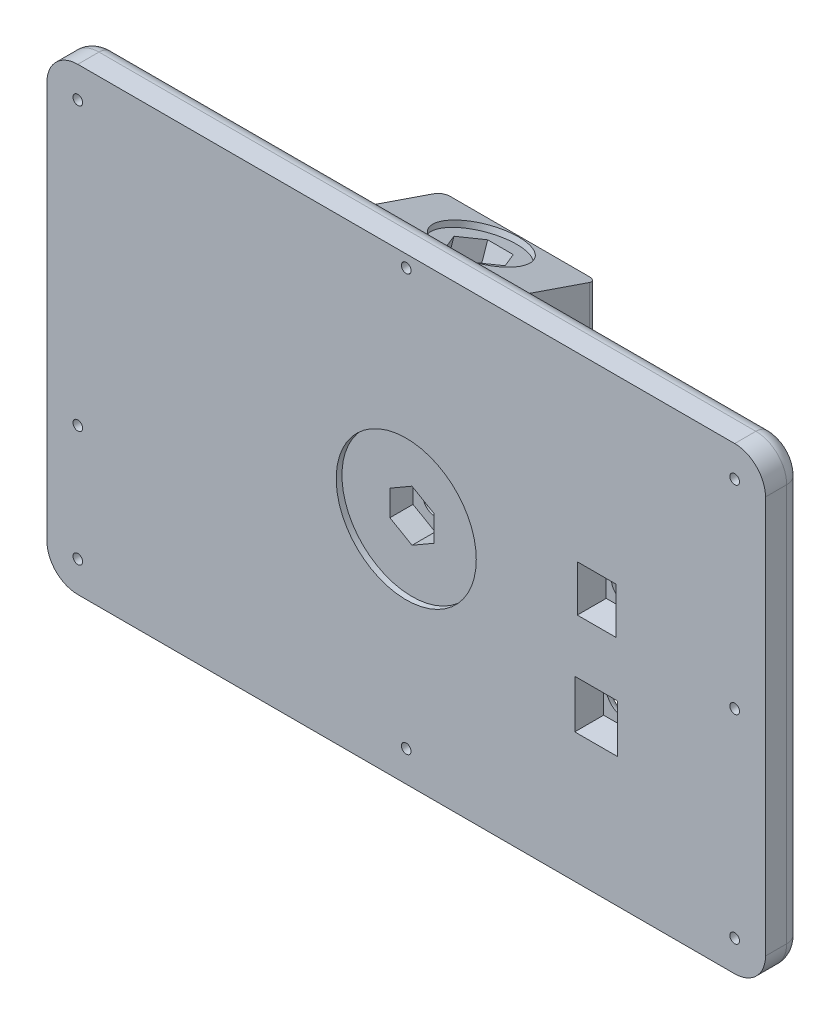
SolidWorks part; units mm, degrees
ref_plane "Front Plane" through (0, 0, 0) normal (0, 0, 1) x (1, 0, 0)
ref_plane "Top Plane" through (0, 0, 0) normal (0, 1, 0) x (1, 0, 0)
ref_plane "Right Plane" through (0, 0, 0) normal (1, 0, 0) x (0, 0, -1)
sketch "Sketch1" plane through (0, 0, 0) normal (0, 0, 1) x (1, 0, 0)
  line L0 (-89.2392, 47.2125) -> (-89.2392, -53.9075)
  line L1 (-83.1292, 39.4025) -> (73.3008, 39.4025)
  line L2 (-83.1292, 39.4025) -> (-83.1292, -49.7475)
  line L3 (-83.1292, -49.7475) -> (73.3008, -49.7475)
  line L4 (73.3008, 39.4025) -> (73.3008, -49.7475)
  line L5 (-88.7392, 46.7125) -> (76.1808, 46.7125)
  line L6 (-88.7392, 46.7125) -> (-88.7392, -53.4075)
  line L7 (-88.7392, -53.4075) -> (76.1808, -53.4075)
  line L8 (76.1808, 46.7125) -> (76.1808, -53.4075)
  line L9 (-89.2392, -53.9075) -> (76.6808, -53.9075)
  line L10 (76.6808, 47.2125) -> (76.6808, -53.9075)
  line L11 (-89.2392, 47.2125) -> (76.6808, 47.2125)
  line L12 (-98.1292, 46.4025) -> (-98.1292, -56.7475)
  line L13 (-90.1292, -64.7475) -> (80.3008, -64.7475)
  line L14 (88.3008, 46.4025) -> (88.3008, -56.7475)
  line L15 (-90.1292, 54.4025) -> (80.3008, 54.4025)
  line L16 (-98.1292, 54.4025) -> (-98.1292, -64.7475) construction
  line L17 (-98.1292, 54.4025) -> (88.3008, 54.4025) construction
  line L18 (-98.1292, -64.7475) -> (88.3008, -64.7475) construction
  line L19 (88.3008, 54.4025) -> (88.3008, -64.7475) construction
  line L21 (-21.7192, 47.2125) -> (-38.9092, 47.2125)
  line L22 (-21.7192, 47.2125) -> (-21.7192, 48.2125)
  line L23 (-21.7192, 48.2125) -> (-38.9092, 48.2125)
  line L24 (-38.9092, 47.2125) -> (-38.9092, 48.2125)
  line L25 (76.6808, -0.1475) -> (77.6808, -0.1475)
  line L26 (76.6808, -0.1475) -> (76.6808, -12.1175)
  line L27 (76.6808, -12.1175) -> (77.6808, -12.1175)
  line L28 (77.6808, -0.1475) -> (77.6808, -12.1175)
  line L29 (76.6808, -0.1475) -> (74.1808, -0.1475)
  line L30 (76.6808, -0.1475) -> (76.6808, -12.1175)
  line L31 (76.6808, -12.1175) -> (74.1808, -12.1175)
  line L32 (74.1808, -0.1475) -> (74.1808, -12.1175)
  line L33 (-38.9092, 47.2125) -> (-21.7192, 47.2125)
  line L34 (-38.9092, 47.2125) -> (-38.9092, 46.2125)
  line L35 (-38.9092, 46.2125) -> (-21.7192, 46.2125)
  line L36 (-21.7192, 47.2125) -> (-21.7192, 46.2125)
  arc A0 (-98.1292, 46.4025) -> (-90.1292, 54.4025) centre (-90.1292, 46.4025) cw
  arc A1 (-90.1292, -64.7475) -> (-98.1292, -56.7475) centre (-90.1292, -56.7475) cw
  arc A2 (88.3008, -56.7475) -> (80.3008, -64.7475) centre (80.3008, -56.7475) cw
  arc A3 (80.3008, 54.4025) -> (88.3008, 46.4025) centre (80.3008, 46.4025) cw
  circle A4 centre (80.3008, 46.4025) radius 1.25
  circle A5 centre (80.3008, -56.7475) radius 1.25
  circle A6 centre (-90.1292, -56.7475) radius 1.25
  circle A7 centre (-90.1292, 46.4025) radius 1.25
  dimension "D9" = 8
  dimension "D10" = 8
  dimension "D11" = 8
  dimension "D12" = 8
  dimension "D13" = 2.5
  dimension "D14" = 2.5
  dimension "D15" = 2.5
  dimension "D16" = 2.5
  dimension "D1" = 89.15
  dimension "D2" = 156.43
  dimension "D3" = 164.92
  dimension "D4" = 100.12
  dimension "D5" = 3.66
  dimension "D6" = 5.61
  dimension "D17" = 17.19
  dimension "D18" = 98.4
  dimension "D19" = 1
  dimension "D20" = 1
  dimension "D21" = 11.97
  dimension "D22" = 47.36
  dimension "D23" = 2.5
  dimension "D24" = 1
  dimension "D7" = 0.5
  dimension "D8" = 15
extrude "Boss-Extrude3" add sketch "Sketch1" along normal blind 9.5 contours A3 L15 A0 L12 A1 L13 A2 L14 A7 L11 L24 L23 L22 L10 L25 L28 L27 L9 L0 A6 A5 A4 | A7 L0 L9 L10 L31 L8 L7 L6 L5 L34 L11 | L5 L36 L35 L34 L6 L7 L8 L31 L32 L29 L1 L4 L3 L2 | L4 L1 L2 L3 | L11 L36 L5 L8 L29 L10 | L24 L11 L22 L23 | L36 L11 L34 L5 | L36 L5 L34 L35 | L28 L25 L10 L27 | L31 L10 L29 L8 | L29 L32 L31 L8 region at (-88.7929, 45.8545, 0) region at (-30.3142, 47.7125, 0) region at (-30.3142, 46.9625, 0) region at (27.4808, 47.1033, 0) region at (-40.8385, 46.4625, 0) region at (-30.3142, 46.4625, 0) region at (76.4308, -6.1325, 0) region at (77.1808, -6.1325, 0) region at (75.1808, -6.1325, 0) region at (-4.9142, -5.1725, 0) region at (-94.2215, 50.4949, 0)
fillet "Fillet2" radius 4 8 edges at (-95.786, 52.0594, 0) (-4.9142, 54.4025, 0) (85.9577, 52.0594, 0) (88.3008, -5.1725, 0) (85.9577, -62.4043, 0) (-4.9142, -64.7475, 0) (-95.786, -62.4043, 0) (-98.1292, -5.1725, 0)
sketch "Sketch9" plane through (0, 0, 9.5) normal (0, 0, 1) x (1, 0, 0)
  line L0 (49.9629, -31.1294) -> (38.8129, -31.1294)
  line L1 (49.4629, -30.6294) -> (39.3129, -30.6294)
  line L2 (49.4629, -30.6294) -> (49.4629, -19.1294)
  line L3 (49.4629, -19.1294) -> (39.3129, -19.1294)
  line L4 (39.3129, -30.6294) -> (39.3129, -19.1294)
  line L5 (38.8129, -31.1294) -> (38.8129, -18.6294)
  line L6 (49.9629, -18.6294) -> (38.8129, -18.6294)
  line L7 (49.9629, -31.1294) -> (49.9629, -18.6294)
  circle A0 centre (44.3729, -24.1894) radius 5.06
  dimension "D4" = 10.12
  dimension "D1" = 10.15
  dimension "D2" = 11.5
  dimension "D3" = 0.5
extrude "Cut-Extrude5" cut sketch "Sketch9" against normal through all contours A0 region at (44.3729, -24.1894, 9.5)
extrude "Cut-Extrude6" cut sketch "Sketch9<3>" against normal offset from surface (7.5 mm away) 2 contours L0 L5 L6 L7 up to face at (49.4329, -24.1894, 0)
sketch "Sketch9<3>" plane through (0, 0, 9.5) normal (0, 0, 1) x (1, 0, 0) same geometry as "Sketch9"
sketch "Sketch10" plane through (0, 0, 9.5) normal (0, 0, 1) x (1, 0, 0)
  line L0 (49.4862, -4.5541) -> (39.4762, -4.5541)
  line L1 (48.9862, -4.0541) -> (39.9762, -4.0541)
  line L2 (48.9862, -4.0541) -> (48.9862, 6.9259)
  line L3 (48.9862, 6.9259) -> (39.9762, 6.9259)
  line L4 (39.9762, -4.0541) -> (39.9762, 6.9259)
  line L5 (39.4762, -4.5541) -> (39.4762, 7.4259)
  line L6 (49.4862, 7.4259) -> (39.4762, 7.4259)
  line L7 (49.4862, -4.5541) -> (49.4862, 7.4259)
  circle A0 centre (44.4812, 0.4859) radius 3.19
  circle A1 centre (44.4812, 0.4859) radius 3.69
  dimension "D4" = 6.38
  dimension "D1" = 10.98
  dimension "D2" = 9.01
  dimension "D6" = 4.54
  dimension "D7" = 4.505
  dimension "D3" = 0.5
  dimension "D5" = 0.5
extrude "Cut-Extrude7" cut sketch "Sketch10" against normal through all contours A1 A0 | A0 region at (44.4812, 0.4859, 9.5) region at (40.8956, 0.4859, 9.5)
extrude "Cut-Extrude8" cut sketch "Sketch10<3>" against normal offset from surface (7.5 mm away) 2 contours L0 L7 L6 L5 L1 L4 L3 L2 | L4 L1 L2 L3 A1 region at (44.4812, -4.398, 9.5) region at (44.4812, -3.9121, 9.5) up to face at (48.1712, 0.4859, 0)
sketch "Sketch10<3>" plane through (0, 0, 9.5) normal (0, 0, 1) x (1, 0, 0) same geometry as "Sketch10"
fillet "Fillet3" radius 2 2 edges at (49.4329, -24.1894, 0) (48.1712, 0.4859, 0)
sketch "Sketch12" plane through (0, 0, 9.5) normal (0, 0, 1) x (1, 0, 0)
  line L0 (0.8367, -8.4791) -> (0.8249, -1.8454)
  line L1 (0.5865, -8.3352) -> (0.5752, -1.9902)
  line L2 (0.5752, -1.9902) -> (-4.9254, 1.1726)
  line L3 (-4.9254, 1.1726) -> (-10.4148, -2.0097)
  line L4 (-10.4148, -2.0097) -> (-10.4035, -8.3548)
  line L5 (-10.4035, -8.3548) -> (-4.9029, -11.5175)
  line L6 (-4.9029, -11.5175) -> (0.5865, -8.3352)
  line L7 (0.8249, -1.8454) -> (-4.926, 1.4613)
  line L8 (-4.926, 1.4613) -> (-10.6651, -1.8658)
  line L9 (-10.6651, -1.8658) -> (-10.6533, -8.4996)
  line L10 (-10.6533, -8.4996) -> (-4.9024, -11.8062)
  line L11 (-4.9024, -11.8062) -> (0.8367, -8.4791)
  line L12 (-90.1292, -64.7475) -> (80.3008, -64.7475) construction
  line L13 (-98.1292, 46.4025) -> (-98.1292, -56.7475) construction
  circle A0 centre (-4.9142, -5.1725) radius 5.495 construction
  circle A1 centre (-4.9142, -5.1725) radius 3.175
  circle A2 centre (-4.9142, -5.1725) radius 18.175
  dimension "D2" = 6.35
  dimension "D5" = 10.99
  dimension "D3" = 59.575
  dimension "D4" = 93.215
  dimension "D1" = 0.25
  dimension "D6" = 15
extrude "Cut-Extrude9" cut sketch "Sketch12" against normal through all contours A1 region at (-4.9142, -5.1725, 9.5)
extrude "Cut-Extrude10" cut sketch "Sketch12<3>" against normal offset from surface (7.5 mm away) 2 contours L10 L11 L0 L7 L8 L9 L6 L5 L4 L3 L2 L1 | L5 L6 L1 L2 L3 L4 A1 region at (-2.1209, -9.9908, 9.5) region at (-2.2424, -9.7811, 9.5) up to face at (-1.7392, -5.1725, 0)
sketch "Sketch12<3>" plane through (0, 0, 9.5) normal (0, 0, 1) x (1, 0, 0) same geometry as "Sketch12"
extrude "Cut-Extrude11" cut sketch "Sketch12<4>" against normal blind 1.5 contours A2 L11 L10 L9 L8 L7 L0 region at (-22.5751, -5.1725, 9.5)
sketch "Sketch12<4>" plane through (0, 0, 9.5) normal (0, 0, 1) x (1, 0, 0) same geometry as "Sketch12"
sketch "Sketch13" plane through (0, 0, 0) normal (0, 0, -1) x (-1, 0, 0)
  line L0 (90.1292, 50.4025) -> (-80.3008, 50.4025) construction
  line L1 (24.9142, 25.4025) -> (-15.0858, 25.4025)
  line L2 (24.9142, 25.4025) -> (24.9142, 50.4025)
  line L3 (24.9142, 50.4025) -> (-15.0858, 50.4025)
  line L4 (-15.0858, 25.4025) -> (-15.0858, 50.4025)
  line L5 (-84.3008, 46.4025) -> (-84.3008, -56.7475) construction
  dimension "D1" = 40
  dimension "D2" = 25
  dimension "D3" = 69.215
extrude "Boss-Extrude10" add sketch "Sketch13" along normal blind 20
sketch "Sketch14" plane through (15.0858, 0, 0) normal (1, 0, 0) x (0, 0, -1)
  line L0 (0, 50.4025) -> (20, 43.5424)
  line L1 (20, 50.4025) -> (0, 50.4025) construction
  line L2 (20, 50.4025) -> (20, 25.4025) construction
  line L3 (20, 43.5424) -> (20, 50.4025)
  line L4 (20, 50.4025) -> (0, 50.4025)
extrude "Cut-Extrude12" cut sketch "Sketch14" against normal through all
sketch "Sketch15" plane through (0, 45.0967, -15.4685) normal (0, 0.9459, -0.3245) x (1, 0, 0)
  line L0 (1.7254, -5.7793) -> (-1.5944, -0.0293)
  line L1 (1.4367, -5.7793) -> (-1.7387, -0.2793)
  line L2 (-1.7387, -0.2793) -> (-8.0896, -0.2793)
  line L3 (-8.0896, -0.2793) -> (-11.265, -5.7793)
  line L4 (-11.265, -5.7793) -> (-8.0896, -11.2793)
  line L5 (-8.0896, -11.2793) -> (-1.7387, -11.2793)
  line L6 (-1.7387, -11.2793) -> (1.4367, -5.7793)
  line L7 (-1.5944, -0.0293) -> (-8.2339, -0.0293)
  line L8 (-8.2339, -0.0293) -> (-11.5537, -5.7793)
  line L9 (-11.5537, -5.7793) -> (-8.2339, -11.5293)
  line L10 (-8.2339, -11.5293) -> (-1.5944, -11.5293)
  line L11 (-1.5944, -11.5293) -> (1.7254, -5.7793)
  line L13 (15.0858, 4.7907) -> (-24.9142, 4.7907) construction
  line L14 (15.0858, -16.3531) -> (15.0858, 4.7907) construction
  circle A0 centre (-4.9142, -5.7793) radius 5.5 construction
  circle A1 centre (-4.9142, -5.7793) radius 3.175
  circle A2 centre (-4.9142, -5.7793) radius 10.175
  dimension "D2" = 11
  dimension "D3" = 6.35
  dimension "D5" = 10.57
  dimension "D6" = 20
  dimension "D1" = 0.25
  dimension "D4" = 7
extrude "Cut-Extrude13" cut sketch "Sketch15" against normal blind 1.5 contours A2 L11 L10 L9 L8 L7 L0 | L10 L11 L0 L7 L8 L9 L6 L5 L4 L3 L2 L1 | L5 L6 L1 L2 L3 L4 A1 | A1 region at (-0.0867, 47.8761, -7.3654) region at (-0.2965, 47.8368, -7.48) region at (-4.9142, 46.9718, -10.0018) region at (-14.8014, 46.9718, -10.0018)
extrude "Cut-Extrude14" cut sketch "Sketch15<3>" against normal blind 6 from surface contours L10 L11 L0 L7 L8 L9 L6 L5 L4 L3 L2 L1 | L5 L6 L1 L2 L3 L4 A1 | A1 region at (-0.0867, 47.8761, -7.3654) region at (-0.2965, 47.8368, -7.48) region at (-4.9142, 46.9718, -10.0018) starting at face at (-4.9142, 48.8543, 0.1094)
sketch "Sketch15<3>" plane through (0, 45.0967, -15.4685) normal (0, 0.9459, -0.3245) x (1, 0, 0) same geometry as "Sketch15"
extrude "Cut-Extrude15" cut sketch "Sketch15<5>" against normal blind 4 from surface contours A1 region at (-4.9142, 46.9718, -10.0018) starting at face at (-4.9142, 39.8776, -7.5684)
sketch "Sketch15<5>" plane through (0, 45.0967, -15.4685) normal (0, 0.9459, -0.3245) x (1, 0, 0) same geometry as "Sketch15"
sketch "Sketch16" plane through (0, 0, 9.5) normal (0, 0, 1) x (1, 0, 0)
  line L0 (-90.1292, 54.4025) -> (80.3008, 54.4025) construction
  line L1 (-90.1292, -64.7475) -> (80.3008, -64.7475) construction
  line L3 (-98.1292, 46.4025) -> (-98.1292, -56.7475) construction
  line L4 (88.3008, 46.4025) -> (88.3008, -56.7475) construction
  circle A0 centre (-4.9142, -56.7475) radius 1.25
  circle A1 centre (80.3008, -5.1725) radius 1.25
  circle A2 centre (-4.9142, 51.2525) radius 1.25
  circle A3 centre (-90.1292, -26.7475) radius 1.25
  dimension "D1" = 2.5
  dimension "D2" = 2.5
  dimension "D3" = 2.5
  dimension "D4" = 2.5
  dimension "D5" = 3.15
  dimension "D6" = 8
  dimension "D7" = 93.215
  dimension "D8" = 8
  dimension "D9" = 59.575
  dimension "D10" = 8
  dimension "D11" = 38
extrude "Cut-Extrude16" cut sketch "Sketch16" against normal through all
fillet "Fillet4" radius 2 8 edges at (15.0858, 37.9025, 0) (-24.9142, 37.9025, 0) (15.0858, 25.4025, -10) (-4.9142, 25.4025, 0) (15.0858, 34.4725, -20) (-24.9142, 25.4025, -10) (-24.9142, 34.4725, -20) (-4.9142, 25.4025, -20)
